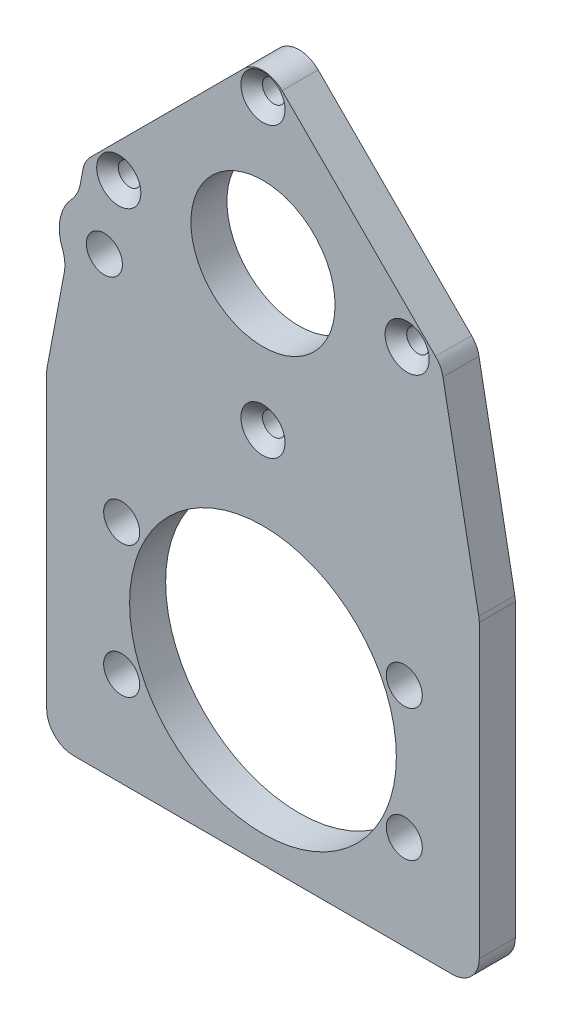
SolidWorks part; units mm, degrees
ref_plane "Front Plane" through (0, 0, 0) normal (0, 0, 1) x (1, 0, 0)
ref_plane "Top Plane" through (0, 0, 0) normal (0, 1, 0) x (1, 0, 0)
ref_plane "Right Plane" through (0, 0, 0) normal (1, 0, 0) x (0, 0, -1)
ref_plane "Plane1" through (0, 0, 171.45) normal (0, 0, 1) x (1, 0, 0)
sketch "Sketch1" plane through (0, 0, 171.45) normal (0, 0, 1) x (1, 0, 0)
  line L0 (0, 762.7561) -> (0, 826.2561) construction
  line L1 (-31.75, 743.7061) -> (31.75, 743.7061) construction
  line L4 (38.1, 791.0136) -> (31.4309, 826.2561)
  line L5 (-38.1, 791.0136) -> (38.1, 791.0136) construction
  line L6 (-38.1, 791.0136) -> (-38.1, 734.4986)
  line L7 (-38.1, 734.4986) -> (38.1, 734.4986)
  line L13 (-31.4309, 826.2561) -> (0, 857.687)
  line L17 (-31.4309, 826.2561) -> (31.4309, 826.2561) construction
  line L18 (0, 794.8252) -> (0, 857.687) construction
  line L24 (0, 762.7561) -> (-24.8906, 774.3628) construction
  line L25 (31.75, 781.8061) -> (-31.75, 781.8061) construction
  line L26 (0, 794.8252) -> (31.4309, 826.2561) construction
  line L27 (31.4309, 826.2561) -> (0, 857.687)
  line L29 (-31.75, 743.7061) -> (31.75, 743.7061) construction
  line L30 (31.75, 781.8061) -> (-31.75, 781.8061) construction
  line L31 (0, 762.7561) -> (23.495, 762.7561) construction
  line L32 (38.1, 791.0136) -> (38.1, 734.4986)
  line L33 (-38.1, 791.0136) -> (38.1, 734.4986) construction
  line L34 (-38.1, 734.4986) -> (38.1, 791.0136) construction
  line L35 (-31.4309, 826.2561) -> (-38.1, 791.0136)
  circle A0 centre (0, 762.7561) radius 22.225 construction
  circle A1 centre (0, 762.7561) radius 22.225 construction
  circle A4 centre (0, 762.7561) radius 23.495
  circle A5 centre (-24.8906, 774.3628) radius 3.175
  circle A8 centre (24.8906, 774.3628) radius 3.175
  circle A9 centre (0, 826.2561) radius 12.7
  circle A10 centre (-25.4, 826.2561) radius 1.9844
  circle A11 centre (0, 851.6561) radius 1.9844
  circle A12 centre (25.4, 826.2561) radius 1.9844
  circle A13 centre (0, 800.8561) radius 1.9844
  circle A14 centre (24.8906, 751.1495) radius 3.175
  circle A15 centre (-24.8906, 751.1495) radius 3.175
  point P7 (0, 786.2511)
  point P9 (24.765, 736.075)
  point P13 (-21.2937, 772.6856)
  point P42 (0, 826.2561)
  dimension "D4" = 6.35
  dimension "D6" = 25.4
  dimension "D10" = 3.9688
  dimension "D2" = 1.27
  dimension "D5" = 28.2575
  dimension "D3" = 3.9688
  dimension "D7" = 65
  dimension "D8" = 44.45
  dimension "D9" = 25.4
  dimension "D12" = 63.5
  dimension "D13" = 76.2
  dimension "D11" = 4
extrude "Boss-Extrude1" add sketch "Sketch1" along normal blind 6.35 contours A14 A4 A8 | A4 L6 L7 L32 | A15 A4 A5 | A15 A4 | A14 A4 | A8 | A5 | A4 L32 L4 L27 L13 L35 L6 A13 A12 A11 A10 A9 region at (0, 790.6868, 171.45)
fillet "Fillet1" radius 4.7625 7 edges at (0, 857.687, 174.625) (-31.4309, 826.2561, 174.625) (31.4309, 826.2561, 174.625) (38.1, 791.0136, 174.625) (38.1, 734.4986, 174.625) (-38.1, 734.4986, 174.625) (-38.1, 791.0136, 174.625)
sketch "Sketch2" plane through (0, 0, 177.8) normal (0, 0, 1) x (1, 0, 0)
  line L0 (40.1484, 790.1727) -> (10.576, 833.4782) construction
  line L1 (-18.9358, 810.6378) -> (-12.1064, 830.4329) construction
  circle A0 centre (0, 826.2561) radius 12.8066 construction
  circle A1 centre (0, 762.7561) radius 48.6165 construction
  arc A2 (10.576, 833.4782) -> (-12.1064, 830.4329) centre (0, 826.2561) ccw construction
  arc A3 (-23.3627, 805.3912) -> (40.1484, 790.1727) centre (0, 762.7561) ccw construction
  circle A4 centre (-27.94, 813.7443) radius 3.175
  arc A5 (-23.3627, 805.3912) -> (-18.9358, 810.6378) centre (-27.94, 813.7443) ccw construction
  circle A7 centre (-27.94, 813.7443) radius 7.9375
  dimension "D1" = 6.35
  dimension "D2" = 9.525
  dimension "D4" = 15.875
  dimension "D3" = 27.94
extrude "Cut-Extrude1" cut sketch "Sketch2" against normal up to surface (6.35 mm away) contours A4 region at (-27.94, 813.7443, 177.8) up to face at (28.0656, 774.3628, 171.45)
extrude "Boss-Extrude2" add sketch "Sketch2<3>" against normal up to surface (6.35 mm away) contours A7 A4 | A7 region at (-35.653, 813.7443, 177.8) up to face at (-24.765, 813.7443, 171.45)
sketch "Sketch2<3>" plane through (0, 0, 177.8) normal (0, 0, 1) x (1, 0, 0) same geometry as "Sketch2"
fillet "Fillet2" radius 6.35 2 edges at (-34.6122, 809.4448, 174.625) (-32.5799, 820.1844, 174.625)
chamfer "Chamfer1" distance 1.905 angle 45 4 edges at (1.9844, 851.6561, 177.8) (27.3844, 826.2561, 177.8) (1.9844, 800.8561, 177.8) (-23.4156, 826.2561, 177.8)
